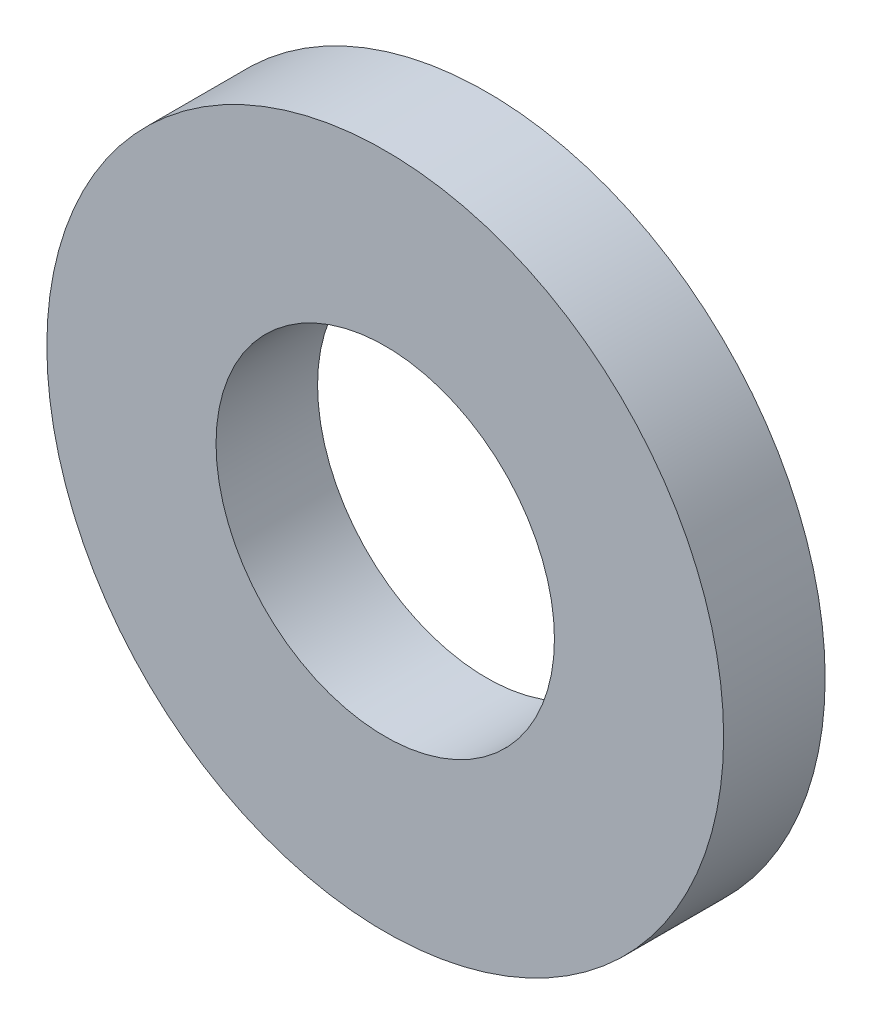
SolidWorks part; units mm, degrees
material "Бронза с оловом"
ref_plane "Спереди" through (0, 0, 0) normal (0, 0, 1) x (1, 0, 0)
ref_plane "Сверху" through (0, 0, 0) normal (0, 1, 0) x (1, 0, 0)
ref_plane "Справа" through (0, 0, 0) normal (1, 0, 0) x (0, 0, -1)
sketch "Эскиз1" plane through (0, 0, 0) normal (0, 0, 1) x (1, 0, 0)
  circle A0 centre (0, 0) radius 2.5
  circle A1 centre (0, 0) radius 5
extrude "Бобышка-Вытянуть1" add sketch "Эскиз1" along normal blind 1.5
